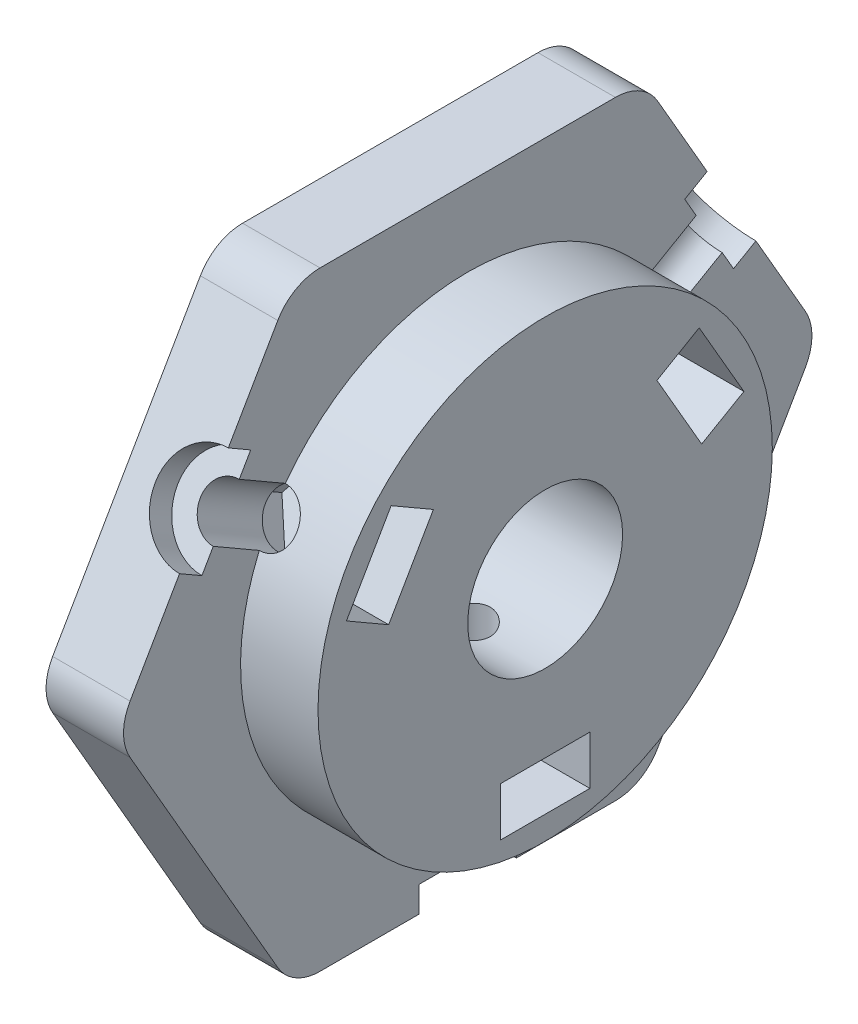
SolidWorks part; units mm, degrees
ref_plane "Front Plane" through (0, 0, 0) normal (0, 0, 1) x (1, 0, 0)
ref_plane "Top Plane" through (0, 0, 0) normal (0, 1, 0) x (1, 0, 0)
ref_plane "Right Plane" through (0, 0, 0) normal (1, 0, 0) x (0, 0, -1)
sketch "Sketch1" plane through (0, 0, 0) normal (1, 0, 0) x (0, 0, -1)
  line L1 (-10.8152, 18.7325) -> (-21.6304, 0)
  line L2 (-21.6304, 0) -> (-10.8152, -18.7325)
  line L3 (-10.8152, -18.7325) -> (10.8152, -18.7325)
  line L4 (10.8152, -18.7325) -> (21.6304, 0)
  line L5 (21.6304, 0) -> (10.8152, 18.7325)
  line L6 (10.8152, 18.7325) -> (-10.8152, 18.7325)
  circle A0 centre (0, 0) radius 18.7325 construction
  dimension "D1" = 37.465
extrude "Boss-Extrude1" add sketch "Sketch1" along normal blind 4.7625
sketch "Sketch2" plane through (4.7625, 0, 0) normal (1, 0, 0) x (0, 0, -1)
  circle A0 centre (0, 0) radius 13.97
  dimension "D1" = 27.94
extrude "Boss-Extrude2" add sketch "Sketch2" along normal blind 4.7625
sketch "Sketch3" plane through (0, -18.7325, 0) normal (0, -1, 0) x (1, 0, 0)
  line L0 (4.7625, 10.8152) -> (4.7625, -10.8152) construction
  circle A0 centre (4.7625, 0) radius 3
  dimension "D1" = 6
extrude "Cut-Extrude1" cut sketch "Sketch3" against normal blind 1.5875
ref_axis "Axis1" through (9.525, 0, 0) along (-1, 0, 0)
ref_plane "Plane1" through (0, 0, 0) normal (0, -1, 0) x (-1, 0, 0)
sketch "Sketch6" plane through (0, 0, 0) normal (0, -1, 0) x (-1, 0, 0)
  line L0 (-6.3502, 2.75) -> (-9.525, 2.75)
  line L1 (-7.9379, 0) -> (-6.3502, -2.75) construction
  line L2 (-6.3502, -2.75) -> (-3.1748, -2.75)
  line L3 (-3.1748, -2.75) -> (-1.5871, 0)
  line L4 (-1.5871, 0) -> (-3.1748, 2.75)
  line L5 (-3.1748, 2.75) -> (-6.3502, 2.75)
  line L6 (-6.3502, 2.75) -> (-7.9379, 0) construction
  line L7 (-9.525, 13.97) -> (-9.525, -13.97) construction
  line L8 (-9.525, 2.75) -> (-9.525, -2.75)
  line L9 (-9.525, -2.75) -> (-6.3502, -2.75)
  circle A0 centre (-4.7625, 0) radius 2.75 construction
  arc A3 (-4.7625, -3) -> (-4.7625, 3) centre (-4.7625, 0) ccw construction
  point P13 (0, 0)
  dimension "D1" = 5.5
extrude "Cut-Extrude4" cut sketch "Sketch6" along normal blind 3 from offset 9.525
sketch "Sketch4" plane through (0, -17.145, 0) normal (0, -1, 0) x (1, 0, 0)
  line L0 (4.7625, 3) -> (4.7625, -3) construction
  circle A0 centre (4.7625, 0) radius 1.6
  dimension "D1" = 3.2
extrude "Cut-Extrude2" cut sketch "Sketch4" against normal up to surface (7.62 mm away) up to face at (5.3973, -9.525, 0)
sketch "Sketch5" plane through (0, -17.145, 0) normal (0, -1, 0) x (1, 0, 0)
  circle A0 centre (4.7625, 0) radius 1.375
  dimension "D1" = 2.75
extrude "Cut-Extrude3" cut sketch "Sketch5" against normal blind 12.7
pattern_circular "CirPattern3" count 3 over 360 about axis through (9.525, 0, 0) along (-1, 0, 0) of "Cut-Extrude3", "Cut-Extrude2", "Cut-Extrude4", "Cut-Extrude1"
fillet "Fillet1" radius 3 6 edges at (2.3813, 18.7325, 10.8152) (2.3813, 0, 21.6304) (2.3813, -18.7325, 10.8152) (2.3813, 18.7325, -10.8152) (2.3813, 0, -21.6304) (2.3813, -18.7325, -10.8152)
sketch "Sketch7" plane through (9.525, 0, 0) normal (1, 0, 0) x (0, 0, -1)
  circle A0 centre (0, 0) radius 4.7625
  dimension "D1" = 9.525
extrude "Cut-Extrude5" cut sketch "Sketch7" against normal through all
